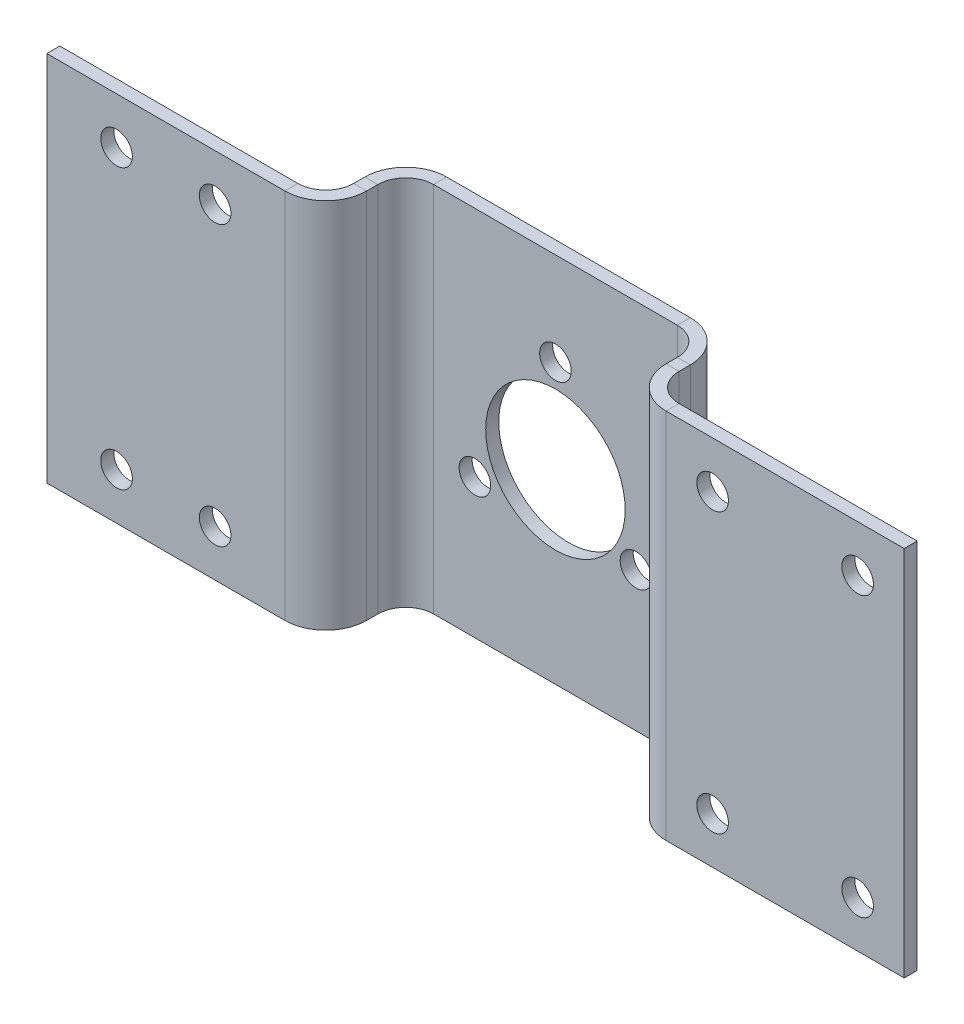
SolidWorks part; units mm, degrees
note: The reader was unsure of these and kept them because the rebuilt part matched: flange length of "Edge-Flange1", "Edge-Flange2", "Edge-Flange3", "Edge-Flange4".
ref_plane "Front Plane" through (0, 0, 0) normal (0, 0, 1) x (1, 0, 0)
ref_plane "Top Plane" through (0, 0, 0) normal (0, 1, 0) x (1, 0, 0)
ref_plane "Right Plane" through (0, 0, 0) normal (1, 0, 0) x (0, 0, -1)
sketch "Sketch6" plane through (0, 0, 0) normal (0, 0, 1) x (1, 0, 0)
  line L1 (0, 0) -> (35, 0)
  line L2 (0, 0) -> (0, 40)
  line L3 (0, 40) -> (35, 40)
  line L4 (35, 0) -> (35, 40)
  dimension "D1" = 35
  dimension "D2" = 40
base flange "Base-Flange2" sketch "Sketch6" thickness 1.4 reverse thickness direction no parameters "D1"=3
edge flange "Edge-Flange1" sketch "Sketch15" flange angle 90 flange length 10 flange position material inside bend radius 3 thickness 1.4 relief rectangular parameters "D6"=10
sketch "Sketch15" plane through (0, 0, 0) normal (-1, 0, 0) x (0, -1, 0)
  line L2 (-40, 0) -> (-40, 8.6)
  line L3 (-40, 8.6) -> (0, 8.6)
  line L4 (0, 8.6) -> (0, 0)
  line L15 (-40, 0) -> (0, 0) construction
  line L16 (-40, 0) -> (0, 0)
bend "EdgeBend1" bend radius 3 bend angle 90 parameters "D5"=1
edge flange "Edge-Flange2" sketch "Sketch18" flange angle 90 flange length 10 flange position material inside bend radius 3 thickness 1.4 relief rectangular parameters "D6"=10
sketch "Sketch18" plane through (35, 0, 0) normal (1, 0, 0) x (0, 1, 0)
  line L2 (0, 0) -> (0, 8.6)
  line L3 (0, 8.6) -> (40, 8.6)
  line L4 (40, 8.6) -> (40, 0)
  line L7 (0, 0) -> (40, 0) construction
  line L8 (0, 0) -> (40, 0)
bend "EdgeBend2" bend radius 3 bend angle 90 parameters "D5"=2
edge flange "Edge-Flange3" sketch "Sketch21" flange angle 90 flange length 30 flange position material inside bend radius 3 thickness 1.4 relief rectangular parameters "D6"=10
sketch "Sketch21" plane through (0, 0, 8.6) normal (0, 0, 1) x (0, 1, 0)
  line L0 (0, 0) -> (40, 0) construction
  line L1 (0, 0) -> (40, 0)
  line L2 (0, 0) -> (0, 28.6)
  line L3 (0, 28.6) -> (40, 28.6)
  line L4 (40, 28.6) -> (40, 0)
bend "EdgeBend3" bend radius 3 bend angle 90 parameters "D5"=3
edge flange "Edge-Flange4" sketch "Sketch24" flange angle 90 flange length 30 flange position material inside bend radius 3 thickness 1.4 relief rectangular parameters "D6"=10
sketch "Sketch24" plane through (35, 0, 8.6) normal (0, 0, 1) x (0, -1, 0)
  line L2 (-40, 0) -> (-40, 28.6)
  line L3 (-40, 28.6) -> (0, 28.6)
  line L4 (0, 28.6) -> (0, 0)
  line L7 (-40, 0) -> (0, 0) construction
  line L8 (-40, 0) -> (0, 0)
bend "EdgeBend4" bend radius 3 bend angle 90 parameters "D5"=4
sketch "Sketch11" plane through (0, 0, 0) normal (0, 0, 1) x (1, 0, 0)
  line L0 (17.5, 20) -> (8.8397, 15) construction
  line L1 (30.6, 40) -> (4.4, 40) construction
  line L2 (17.5, 20) -> (17.5, 30) construction
  line L4 (17.5, 20) -> (26.1603, 15) construction
  line L5 (4.4, 0) -> (4.4, 40) construction
  circle A0 centre (17.5, 20) radius 7.5
  circle A1 centre (17.5, 30) radius 1.7
  circle A2 centre (8.8397, 15) radius 1.7
  circle A3 centre (26.1603, 15) radius 1.7
  point P4 (0, 0)
  point P11 (17.5, 40)
  point P12 (0, 0)
  point P13 (25, 20)
  point P15 (0, 0)
  point P18 (25, 20)
  point P19 (0, 0)
  point P20 (0, 0)
  point P21 (0, 0)
  point P22 (0, 0)
  point P25 (4.4, 20)
  dimension "D1" = 15
  dimension "D4" = 3.4
  dimension "D2" = 10
extrude "Cut-Extrude2" cut sketch "Sketch11" against normal through all both and the other way through all normal cut yes
sketch "Sketch26" plane through (0, 0, 8.6) normal (0, 0, 1) x (1, 0, 0)
  line L0 (-3, 40) -> (-28.6, 40) construction
  line L1 (-28.6, 40) -> (-28.6, 0) construction
  line L2 (-3, 40) -> (-3, 0) construction
  line L3 (-28.6, 0) -> (-3, 0) construction
  circle A0 centre (-21.1, 35) radius 1.7
  circle A1 centre (-10.5, 35) radius 1.7
  circle A2 centre (-21.1, 5) radius 1.7
  circle A3 centre (-10.5, 5) radius 1.7
  dimension "D2" = 3.4
  dimension "D1" = 5
  dimension "D3" = 7.5
  dimension "D4" = 7.5
  dimension "D5" = 5
sketch "Sketch27" plane through (0, 0, 8.6) normal (0, 0, 1) x (1, 0, 0)
  line L4 (38, 0) -> (38, 40) construction
  line L5 (63.6, 0) -> (63.6, 40) construction
  line L6 (63.6, 40) -> (38, 40) construction
  line L7 (38, 0) -> (63.6, 0) construction
  circle A0 centre (43, 35) radius 1.7
  circle A1 centre (58.6, 35) radius 1.7
  circle A2 centre (43, 5) radius 1.7
  circle A3 centre (58.6, 5) radius 1.7
  dimension "D2" = 3.4
  dimension "D1" = 5
  dimension "D3" = 5
  dimension "D4" = 5
  dimension "D5" = 5
extrude "Cut-Extrude3" cut sketch "Sketch26" against normal through all both and the other way through all normal cut yes
extrude "Cut-Extrude4" cut sketch "Sketch27" against normal through all both and the other way through all normal cut yes
sketch "Bend-Lines3" [suppressed] plane through (0, 0, 0) normal (0, 1, 0) x (1, 0, 0)
sketch "Bounding-Box3" [suppressed] plane through (0, 0, 0) normal (0, 1, 0) x (1, 0, 0)
sheet metal parameters "Sheet-Metal3" thickness 1.4 parameters "D1"=3
flat pattern "Flat-Pattern3" [suppressed]
sketch "Bend-Lines4" plane through (0, 0, 0) normal (0, 1, 0) x (1, 0, 0)
sketch3d "Bounding-Box4" [suppressed]
  line L0 (0, 0, 0) -> (-50, 0, 0) construction
  line L1 (0, 40, 0) -> (-50, 40, 0) construction
  line L2 (0, 0, 0) -> (0, 40, 0) construction
  line L3 (-50, 0, 0) -> (-50, 40, 0) construction
sheet metal parameters "Sheet-Metal5" thickness 1.4 parameters "D1"=3
flat pattern "Flat-Pattern3"
sketch "Bend-Lines4" plane through (0, 0, 0) normal (0, 0, 1) x (1, 0, 0)
  line L0 (1.494, 40) -> (1.494, 0) construction
  line L1 (1.494, 40) -> (1.494, 0) construction
sketch3d "Bounding-Box4" [suppressed]
  line L0 (-22.0119, 0, 0) -> (50, 0, 0) construction
  line L1 (-22.0119, 40, 0) -> (50, 40, 0) construction
  line L2 (-22.0119, 0, 0) -> (-22.0119, 40, 0) construction
  line L3 (50, 0, 0) -> (50, 40, 0) construction
bend of the flat pattern "Flatten-<EdgeBend1>1"
sheet metal parameters "Sheet-Metal6" thickness 1.4 parameters "D1"=3
flat pattern "Flat-Pattern3"
sketch "Bend-Lines4" plane through (0, 0, 0) normal (0, 0, 1) x (1, 0, 0)
  line L0 (1.494, 40) -> (1.494, 0) construction
  line L1 (1.494, 40) -> (1.494, 0) construction
  line L2 (33.506, 0) -> (33.506, 40) construction
  line L3 (33.506, 0) -> (33.506, 40) construction
sketch3d "Bounding-Box4" [suppressed]
  line L0 (-2.0119, 0, 0) -> (57.0119, 0, 0) construction
  line L1 (-2.0119, 40, 0) -> (57.0119, 40, 0) construction
  line L2 (-2.0119, 0, 0) -> (-2.0119, 40, 0) construction
  line L3 (57.0119, 0, 0) -> (57.0119, 40, 0) construction
bend of the flat pattern "Flatten-<EdgeBend1>1"
bend of the flat pattern "Flatten-<EdgeBend2>1"
sheet metal parameters "Sheet-Metal7" thickness 1.4 parameters "D1"=3
flat pattern "Flat-Pattern3"
sketch "Bend-Lines4" plane through (0, 0, 0) normal (0, 0, 1) x (1, 0, 0)
  line L0 (1.494, 40) -> (1.494, 0) construction
  line L1 (1.494, 40) -> (1.494, 0) construction
  line L2 (33.506, 0) -> (33.506, 40) construction
  line L3 (33.506, 0) -> (33.506, 40) construction
  line L4 (-20.5179, 40) -> (-20.5179, 0) construction
  line L5 (-20.5179, 40) -> (-20.5179, 0) construction
sketch3d "Bounding-Box4" [suppressed]
  line L0 (-49.0239, 0, 0) -> (57.0119, 0, 0) construction
  line L1 (-49.0239, 40, 0) -> (57.0119, 40, 0) construction
  line L2 (-49.0239, 0, 0) -> (-49.0239, 40, 0) construction
  line L3 (57.0119, 0, 0) -> (57.0119, 40, 0) construction
bend of the flat pattern "Flatten-<EdgeBend1>1"
bend of the flat pattern "Flatten-<EdgeBend2>1"
bend of the flat pattern "Flatten-<EdgeBend3>1"
sheet metal parameters "Sheet-Metal8" thickness 1.4 parameters "D1"=3
flat pattern "Flat-Pattern3"
sketch "Bend-Lines4" plane through (0, 0, 0) normal (0, 0, 1) x (1, 0, 0)
  line L0 (1.494, 40) -> (1.494, 0) construction
  line L1 (1.494, 40) -> (1.494, 0) construction
  line L2 (48.506, 0) -> (48.506, 40) construction
  line L3 (48.506, 0) -> (48.506, 40) construction
  line L4 (-20.5179, 40) -> (-20.5179, 0) construction
  line L5 (-20.5179, 40) -> (-20.5179, 0) construction
  line L6 (70.5179, 0) -> (70.5179, 40) construction
  line L7 (70.5179, 0) -> (70.5179, 40) construction
sketch3d "Bounding-Box4" [suppressed]
  line L0 (-49.0239, 0, 0) -> (99.0239, 0, 0) construction
  line L1 (-49.0239, 40, 0) -> (99.0239, 40, 0) construction
  line L2 (-49.0239, 0, 0) -> (-49.0239, 40, 0) construction
  line L3 (99.0239, 0, 0) -> (99.0239, 40, 0) construction
bend of the flat pattern "Flatten-<EdgeBend1>1"
bend of the flat pattern "Flatten-<EdgeBend2>1"
bend of the flat pattern "Flatten-<EdgeBend3>1"
bend of the flat pattern "Flatten-<EdgeBend4>1"
sheet metal parameters "Sheet-Metal9" thickness 1.4 parameters "D1"=3
flat pattern "Flat-Pattern3"
sketch "Bend-Lines4" plane through (0, 0, 0) normal (0, 0, 1) x (1, 0, 0)
  line L0 (1.494, 40) -> (1.494, 0) construction
  line L1 (1.494, 40) -> (1.494, 0) construction
  line L2 (48.506, 0) -> (48.506, 40) construction
  line L3 (48.506, 0) -> (48.506, 40) construction
  line L4 (-20.5179, 40) -> (-20.5179, 0) construction
  line L5 (-20.5179, 40) -> (-20.5179, 0) construction
  line L6 (70.5179, 0) -> (70.5179, 40) construction
  line L7 (70.5179, 0) -> (70.5179, 40) construction
sketch3d "Bounding-Box4" [suppressed]
  line L0 (-49.0239, 0, 0) -> (99.0239, 0, 0) construction
  line L1 (-49.0239, 40, 0) -> (99.0239, 40, 0) construction
  line L2 (-49.0239, 0, 0) -> (-49.0239, 40, 0) construction
  line L3 (99.0239, 0, 0) -> (99.0239, 40, 0) construction
bend of the flat pattern "Flatten-<EdgeBend1>1"
bend of the flat pattern "Flatten-<EdgeBend2>1"
bend of the flat pattern "Flatten-<EdgeBend3>1"
bend of the flat pattern "Flatten-<EdgeBend4>1"
sheet metal parameters "Sheet-Metal10" thickness 1.4 parameters "D1"=3
flat pattern "Flat-Pattern3" [suppressed]
sketch "Bend-Lines4" plane through (0, 0, 0) normal (0, 0, 1) x (1, 0, 0)
  line L0 (1.494, 40) -> (1.494, 0) construction
  line L1 (1.494, 40) -> (1.494, 0) construction
  line L2 (48.506, 0) -> (48.506, 40) construction
  line L3 (48.506, 0) -> (48.506, 40) construction
  line L4 (-20.5179, 40) -> (-20.5179, 0) construction
  line L5 (-20.5179, 40) -> (-20.5179, 0) construction
  line L6 (70.5179, 0) -> (70.5179, 40) construction
  line L7 (70.5179, 0) -> (70.5179, 40) construction
sketch3d "Bounding-Box4" [suppressed]
  line L0 (-49.0239, 0, 0) -> (99.0239, 0, 0) construction
  line L1 (-49.0239, 40, 0) -> (99.0239, 40, 0) construction
  line L2 (-49.0239, 0, 0) -> (-49.0239, 40, 0) construction
  line L3 (99.0239, 0, 0) -> (99.0239, 40, 0) construction
bend of the flat pattern "Flatten-<EdgeBend1>1"
bend of the flat pattern "Flatten-<EdgeBend2>1"
bend of the flat pattern "Flatten-<EdgeBend3>1"
bend of the flat pattern "Flatten-<EdgeBend4>1"
sketch "Sketch27-1" [suppressed] plane through (20.4239, 0, 0) normal (0, 0, 1) x (1, 0, 0)
  line L4 (53, 0) -> (53, 40) construction
  line L5 (78.6, 0) -> (78.6, 40) construction
  line L6 (78.6, 40) -> (-69.4478, 40) construction
  line L7 (-69.4478, 0) -> (78.6, 0) construction
  circle A0 centre (58, 35) radius 1.7
  circle A1 centre (73.6, 35) radius 1.7
  circle A2 centre (58, 5) radius 1.7
  circle A3 centre (73.6, 5) radius 1.7
  dimension "D2" = 3.4
  dimension "D1" = 5
  dimension "D3" = 5
  dimension "D4" = 5
  dimension "D5" = 5
sheet metal parameters "Sheet-Metal11" thickness 1.4 parameters "D1"=3
flat pattern "Flat-Pattern3" [suppressed]
sketch "Bend-Lines4" plane through (0, 0, 0) normal (0, 0, 1) x (1, 0, 0)
  line L0 (1.494, 40) -> (1.494, 0) construction
  line L1 (1.494, 40) -> (1.494, 0) construction
  line L2 (33.506, 0) -> (33.506, 40) construction
  line L3 (33.506, 0) -> (33.506, 40) construction
  line L4 (-5.5179, 40) -> (-5.5179, 0) construction
  line L5 (-5.5179, 40) -> (-5.5179, 0) construction
  line L6 (40.5179, 0) -> (40.5179, 40) construction
  line L7 (40.5179, 0) -> (40.5179, 40) construction
sketch3d "Bounding-Box4" [suppressed]
  line L0 (-34.0239, 0, 0) -> (69.0239, 0, 0) construction
  line L1 (-34.0239, 40, 0) -> (69.0239, 40, 0) construction
  line L2 (-34.0239, 0, 0) -> (-34.0239, 40, 0) construction
  line L3 (69.0239, 0, 0) -> (69.0239, 40, 0) construction
bend of the flat pattern "Flatten-<EdgeBend1>1"
bend of the flat pattern "Flatten-<EdgeBend2>1"
bend of the flat pattern "Flatten-<EdgeBend3>1"
bend of the flat pattern "Flatten-<EdgeBend4>1"
sketch "Sketch27-1" [suppressed] plane through (5.4239, 0, 0) normal (0, 0, 1) x (1, 0, 0)
  line L4 (38, 0) -> (38, 40) construction
  line L5 (63.6, 0) -> (63.6, 40) construction
  line L6 (63.6, 40) -> (-39.4478, 40) construction
  line L7 (-39.4478, 0) -> (63.6, 0) construction
  circle A0 centre (43, 35) radius 1.7
  circle A1 centre (58.6, 35) radius 1.7
  circle A2 centre (43, 5) radius 1.7
  circle A3 centre (58.6, 5) radius 1.7
  dimension "D2" = 3.4
  dimension "D1" = 5
  dimension "D3" = 5
  dimension "D4" = 5
  dimension "D5" = 5
